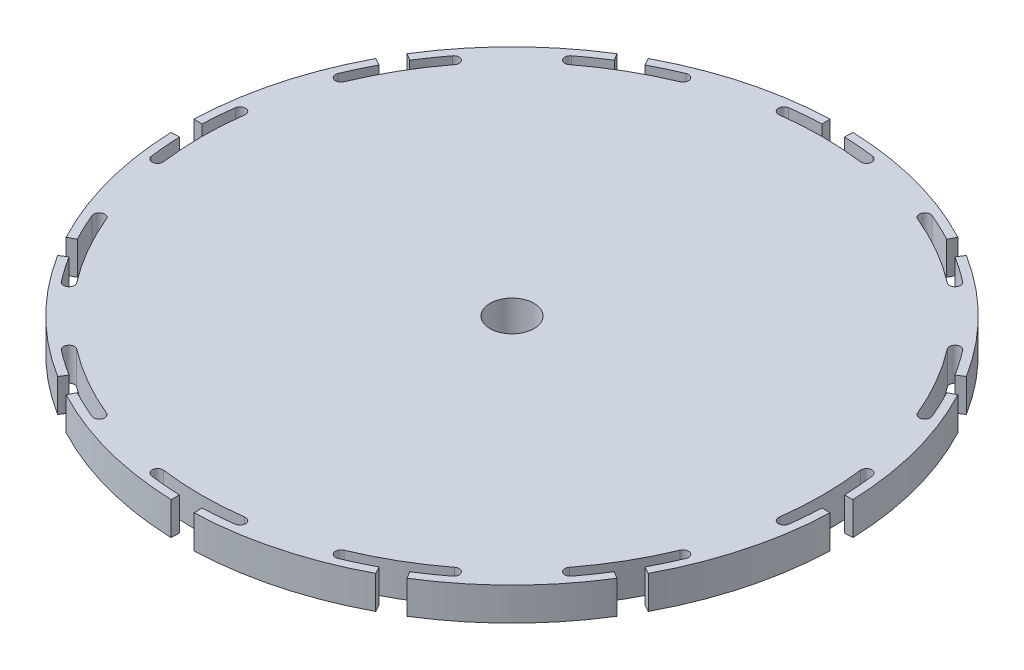
SolidWorks part; units mm, degrees
ref_plane "Front Plane" through (0, 0, 0) normal (0, 0, 1) x (1, 0, 0)
ref_plane "Top Plane" through (0, 0, 0) normal (0, 1, 0) x (1, 0, 0)
ref_plane "Right Plane" through (0, 0, 0) normal (1, 0, 0) x (0, 0, -1)
sketch "Sketch1" plane through (0, 0, 0) normal (0, 1, 0) x (1, 0, 0)
  circle A0 centre (0, 0) radius 60
  dimension "D1" = 120
sketch "Sketch2" plane through (0, 0, 0) normal (0, 1, 0) x (1, 0, 0)
  line L0 (0, 0) -> (0, 60) construction
  line L1 (-2.094, 59.9634) -> (0, 0) construction
  line L2 (0, 0) -> (-7.8316, 59.4867) construction
  line L3 (-2.094, 59.9634) -> (-2.0416, 58.4644)
  line L4 (0, 0) -> (7.8316, 59.4867) construction
  line L5 (2.094, 59.9634) -> (0, 0) construction
  line L6 (2.094, 59.9634) -> (2.0416, 58.4644)
  arc A0 (7.3747, 56.0166) -> (-7.3747, 56.0166) centre (0, 0) ccw
  circle A1 centre (0, 0) radius 60 construction
  arc A2 (-2.094, 59.9634) -> (2.094, 59.9634) centre (0, 0) cw
  arc A3 (-2.0416, 58.4644) -> (-7.6358, 57.9995) centre (0, 0) ccw
  arc A4 (-7.3747, 56.0166) -> (-7.6358, 57.9995) centre (-7.5053, 57.0081) cw
  arc A5 (7.3747, 56.0166) -> (7.6358, 57.9995) centre (7.5053, 57.0081) ccw
  arc A6 (2.0416, 58.4644) -> (7.6358, 57.9995) centre (0, 0) cw
  point P130 (0, 0)
  dimension "D1" = 15
  dimension "D2" = 2
  dimension "D4" = 1.5
  dimension "D3" = 4
sketch "Sketch3" plane through (0, 0, 0) normal (0, 1, 0) x (1, 0, 0)
  circle A0 centre (0, 0) radius 4
  dimension "D1" = 8
extrude "Wheel Blank" add sketch "Sketch1" along normal blind 6
extrude "T-Slot" cut sketch "Sketch2" along normal through all
pattern_circular "CirPattern" count 12 over 360 about axis through (0, 6, 0) along (0, -1, 0) of "T-Slot"
extrude "Center Hole" cut sketch "Sketch3" along normal blind 6
